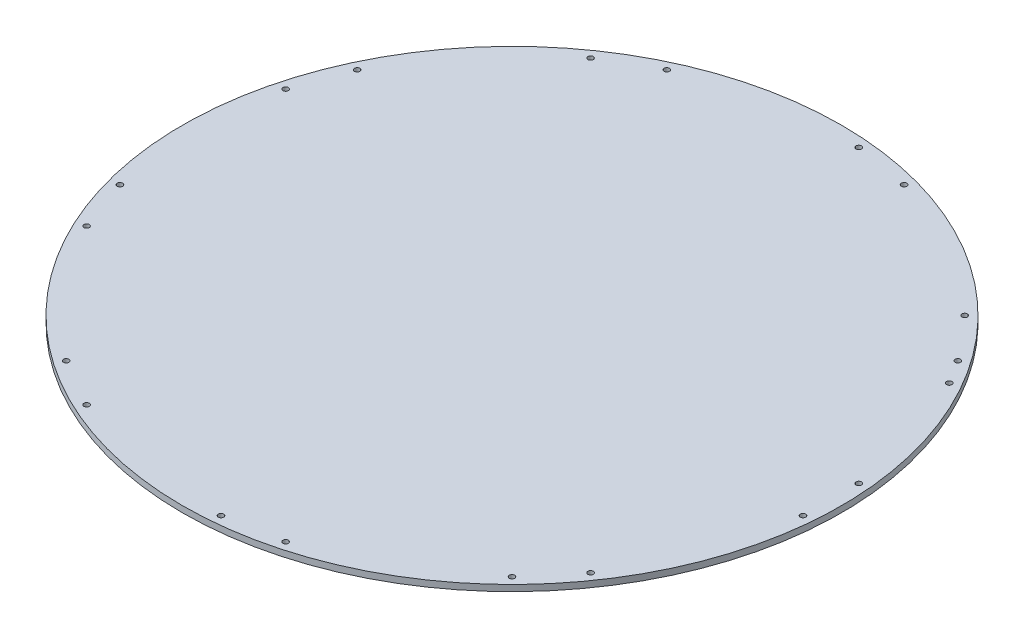
SolidWorks part; units mm, degrees
ref_plane "Front Plane" through (0, 0, 0) normal (0, 0, 1) x (1, 0, 0)
ref_plane "Top Plane" through (0, 0, 0) normal (0, 1, 0) x (1, 0, 0)
ref_plane "Right Plane" through (0, 0, 0) normal (1, 0, 0) x (0, 0, -1)
sketch "Sketch1" plane through (0, 0, 0) normal (0, 1, 0) x (1, 0, 0)
  circle A0 centre (0, 0) radius 309.88
  dimension "D1" = 619.76
extrude "Boss-Extrude1" add sketch "Sketch1" along normal blind 5.842
ref_axis "Axis1" through (0, 6.6675, 0) along (0, -1, 0)
sketch "Sketch2" plane through (0, 5.842, 0) normal (0, 1, 0) x (1, 0, 0)
  line L0 (0, 0) -> (-309.88, 0) construction
  line L1 (0, 0) -> (-290.734, 77.9019) construction
  line L2 (0, 0) -> (-290.734, -77.9019) construction
  line L3 (-154.94, 0) -> (-154.94, -41.516) construction
  line L4 (-154.94, 0) -> (-154.94, 41.516) construction
  circle A1 centre (0, 0) radius 309.88 construction
  circle A2 centre (-290.734, 77.9019) radius 2.5527
  circle A3 centre (-290.734, -77.9019) radius 2.5527
  dimension "D2" = 300.99
  dimension "D3" = 5.1054
  dimension "D1" = 30
extrude "Cut-Extrude1" cut sketch "Sketch2" against normal through all
pattern_circular "CirPattern1" count 9 over 360 about axis through (0, 6.6675, 0) along (0, -1, 0) of "Cut-Extrude1"
sketch "Sketch3" plane through (0, 5.842, 0) normal (0, 1, 0) x (1, 0, 0)
  line L0 (0, 0) -> (309.88, 0) construction
  line L1 (260.665, 150.495) -> (0, 0) construction
  circle A0 centre (260.665, 150.495) radius 2.5527
  circle A1 centre (0, 0) radius 309.88 construction
  circle A2 centre (0, 0) radius 300.99 construction
  dimension "D2" = 5.1054
  dimension "D1" = 30
extrude "Hole_Wire" cut sketch "Sketch3" against normal through all
